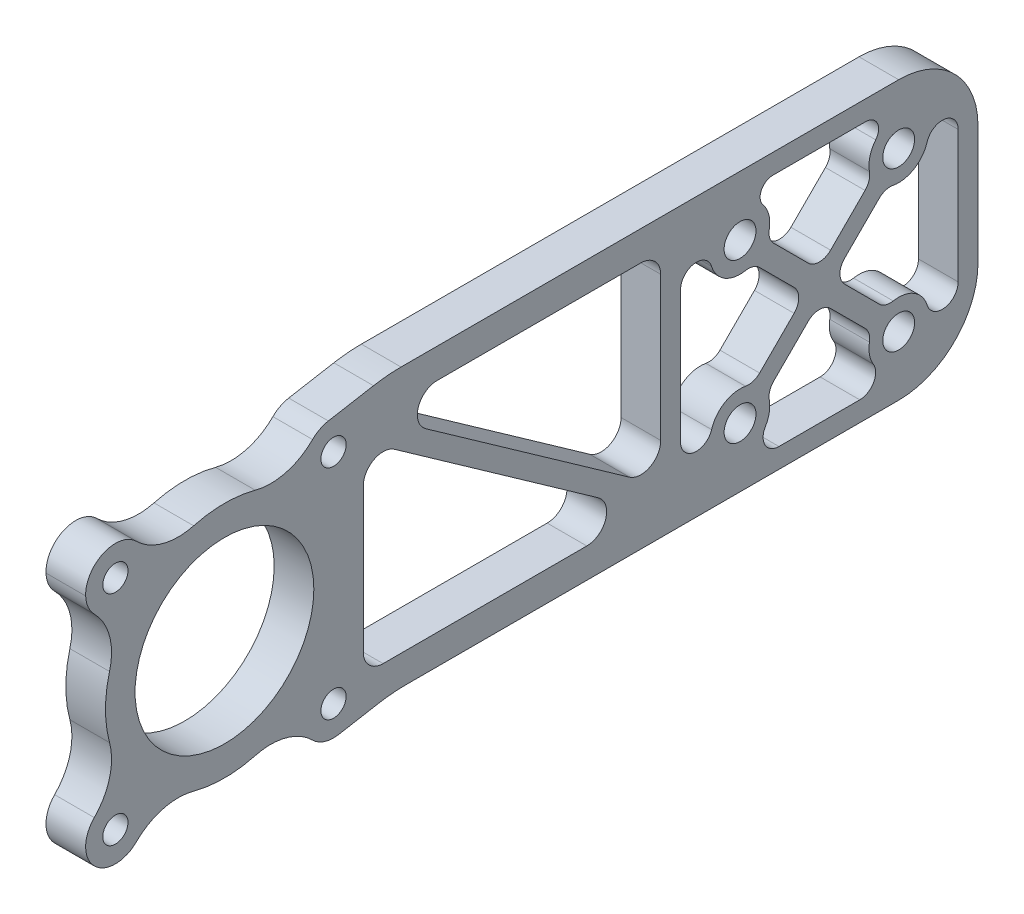
SolidWorks part; units mm, degrees
material "6061-T6 (SS)"
ref_plane "Front" through (0, 0, 0) normal (0, 0, 1) x (1, 0, 0)
ref_plane "Top" through (0, 0, 0) normal (0, 1, 0) x (1, 0, 0)
ref_plane "Right" through (0, 0, 0) normal (1, 0, 0) x (0, 0, -1)
sketch "Sketch1" plane through (0, 0, 0) normal (1, 0, 0) x (0, 0, -1)
  line L0 (0, -23.8125) -> (0, 23.8125)
  line L3 (0, 23.8125) -> (-144.4879, 23.8125)
  line L4 (-144.4879, -23.8125) -> (0, -23.8125)
  line L5 (-144.4879, 23.8125) -> (-144.4879, -23.8125)
  line L6 (-120.65, 23.8125) -> (-120.65, -23.8125) construction
  circle A1 centre (-120.65, 0) radius 14.3129
  point P4 (0, 0)
  dimension "D3" = 28.6258
  dimension "D1" = 9.525
  dimension "D2" = 47.625
  dimension "D5" = 120.65
extrude "Boss-Extrude1" add sketch "Sketch1" along normal blind 6.35
fillet "Fillet1" radius 12.7 4 edges at (3.175, -23.8125, 144.4879) (3.175, 23.8125, 144.4879) (3.175, -23.8125, 0) (3.175, 23.8125, 0)
sketch "Sketch4" plane through (0, 0, 0) normal (-1, 0, 0) x (0, 0, 1)
  point P0 (103.1875, 17.4625)
  point P3 (138.1125, 17.4625)
  point P6 (138.1125, -17.4625)
  point P9 (103.1875, -17.4625)
hole_wizard "#10-32 Tapped Hole1" positions "Sketch4" profile "Sketch3" tap size "#10-32" standard "ANSI Inch" end condition up to next
sketch "Sketch3" plane through (0, 17.4625, 103.1875) normal (0, 1, 0) x (0, 0, 1)
  line L0 (0, 0) -> (0, 6.35)
  line L1 (0, 6.35) -> (2.0193, 6.35)
  line L2 (2.0193, 6.35) -> (2.0193, 0)
  line L5 (2.0193, 0) -> (0, 0)
  line L11 (0, -6.35) -> (0, 107.95) construction
  dimension "Thru Tap Drill Dia." = 4.0386
  dimension "Thru Tap Drill Depth" = 6.35
cosmetic thread "Hole Thread5" parameters "D2"=4.826
cosmetic thread "Hole Thread6" parameters "D2"=4.826
cosmetic thread "Hole Thread7" parameters "D2"=4.826
cosmetic thread "Hole Thread8" parameters "D2"=4.826
sketch "Sketch7" plane through (6.35, 0, 0) normal (1, 0, 0) x (0, 0, -1)
  line L0 (-50.8, 23.8125) -> (-50.8, -23.8125) construction
  line L1 (-12.7, 23.8125) -> (-131.7879, 23.8125) construction
  line L2 (-131.7879, -23.8125) -> (-12.7, -23.8125) construction
  line L4 (0, -11.1125) -> (0, 11.1125) construction
  line L5 (-50.8, -23.8125) -> (-38.1, -11.1125) construction
  line L8 (-12.7, -11.1125) -> (0, -23.8125) construction
  line L9 (0, -11.1125) -> (0, 11.1125) construction
  line L10 (-131.7879, -23.8125) -> (-12.7, -23.8125) construction
  point P0 (-12.7, 14.2875)
  point P2 (-38.1, 14.2875)
  point P4 (-38.1, -11.1125)
  point P6 (-12.7, -11.1125)
  dimension "D1" = 50.8
  dimension "D2" = 25.4
  dimension "D3" = 25.4
  dimension "D4" = 12.7
hole_wizard "#10 Clearance Hole1" positions "Sketch7" profile "Sketch6" hole size "#10" standard "ANSI Inch" end condition up to next
sketch "Sketch6" plane through (6.35, 14.2875, 12.7) normal (0, 1, 0) x (0, 0, -1)
  line L0 (0, 0) -> (0, 6.35)
  line L1 (0, 6.35) -> (2.5527, 6.35)
  line L2 (2.5527, 6.35) -> (2.5527, 0)
  line L5 (2.5527, 0) -> (0, 0)
  line L11 (0, -6.35) -> (0, 107.95) construction
  dimension "Thru Hole Dia." = 5.1054
  dimension "Thru Hole Depth" = 6.35
sketch "Sketch9" plane through (6.35, 0, 0) normal (1, 0, 0) x (0, 0, -1)
  line L0 (0, -20.6375) -> (-89.738, -20.6375)
  line L1 (0, -11.1125) -> (0, 11.1125) construction
  line L2 (-131.7879, -23.8125) -> (-12.7, -23.8125) construction
  arc A0 (-89.738, -20.6375) -> (-96.8375, -23.8125) centre (-89.738, -30.1625) ccw
  circle A1 centre (-103.1875, -17.4625) radius 2.0193 construction
  dimension "D1" = 9.525
  dimension "D3" = 6.35
  dimension "D2" = 3.175
extrude "Cut-Extrude2" cut sketch "Sketch9" against normal through all and the other way through all
other "DeleteFace1" face at (3.175, -16.1064, 1.6373) and patch yes
fillet "Fillet3" radius 12.7 2 edges at (3.175, -20.6375, 0) (3.175, -23.8125, 96.8375)
sketch "Sketch8" plane through (6.35, 0, 0) normal (1, 0, 0) x (0, 0, -1)
  line L0 (-86.5918, 19.05) -> (-53.975, 19.05)
  line L1 (-98.425, 10.3281) -> (-98.425, -12.7)
  line L3 (-95.25, -15.875) -> (-62.6332, -15.875)
  line L4 (-50.8, -7.1531) -> (-50.8, 15.875)
  line L6 (-12.7, 23.8125) -> (-131.7879, 23.8125) construction
  line L8 (0, -7.9375) -> (0, 11.1125) construction
  line L9 (-88.423, 13.2813) -> (-55.8062, -9.7468)
  line L10 (-60.802, -10.1063) -> (-93.4188, 12.9218)
  line L11 (-98.425, 16.4563) -> (-96.5938, 19.05) construction
  line L16 (-33.8025, 12.235) -> (-25.4, 3.8326)
  line L17 (-16.9975, -9.06) -> (-25.4, -0.6576)
  line L18 (-16.9975, 12.235) -> (-25.4, 3.8326)
  line L19 (-14.7525, 9.99) -> (-23.1549, 1.5875)
  line L20 (-23.1549, 1.5875) -> (-14.7525, -6.815)
  line L21 (-27.6451, 1.5875) -> (-36.0475, 9.99)
  line L22 (-27.6451, 1.5875) -> (-36.0475, -6.815)
  line L23 (-25.4, -0.6576) -> (-33.8025, -9.06)
  line L24 (-32.854, 20.6375) -> (-17.946, 20.6375)
  line L25 (-47.625, 12.1576) -> (-47.625, -8.9826)
  line L26 (-31.8702, -17.4625) -> (-18.9298, -17.4625)
  line L30 (-89.738, -20.6375) -> (-12.7, -20.6375) construction
  line L31 (-3.175, 12.1576) -> (-3.175, -8.9826)
  line L32 (0, -7.9375) -> (0, 11.1125) construction
  circle A0 centre (-103.1875, 17.4625) radius 2.0193 construction
  arc A1 (-93.4188, 12.9218) -> (-98.425, 10.3281) centre (-95.25, 10.3281) ccw
  arc A2 (-98.425, -12.7) -> (-95.25, -15.875) centre (-95.25, -12.7) ccw
  arc A3 (-60.802, -10.1063) -> (-62.6332, -15.875) centre (-62.6332, -12.7) cw
  arc A4 (-55.8062, -9.7468) -> (-50.8, -7.1531) centre (-53.975, -7.1531) ccw
  arc A5 (-53.975, 19.05) -> (-50.8, 15.875) centre (-53.975, 15.875) cw
  arc A6 (-88.423, 13.2813) -> (-86.5918, 19.05) centre (-86.5918, 15.875) cw
  arc A7 (-33.8025, 12.235) -> (-34.4229, 17.3141) centre (-38.1, 14.2875) ccw
  arc A8 (-14.7525, 9.99) -> (-8.1446, 12.8985) centre (-12.7, 14.2875) ccw
  arc A9 (-16.9975, -9.06) -> (-16.7629, -13.5973) centre (-12.7, -11.1125) ccw
  arc A10 (-36.0475, -6.815) -> (-42.6554, -9.7235) centre (-38.1, -11.1125) ccw
  arc A11 (-8.1446, -9.7235) -> (-14.7525, -6.815) centre (-12.7, -11.1125) ccw
  arc A12 (-42.6554, 12.8985) -> (-36.0475, 9.99) centre (-38.1, 14.2875) ccw
  arc A13 (-16.3771, 17.3141) -> (-16.9975, 12.235) centre (-12.7, 14.2875) ccw
  arc A14 (-34.0371, -13.5973) -> (-33.8025, -9.06) centre (-38.1, -11.1125) ccw
  arc A15 (-17.946, 20.6375) -> (-16.3771, 17.3141) centre (-17.946, 18.6055) cw
  arc A16 (-32.854, 20.6375) -> (-34.4229, 17.3141) centre (-32.854, 18.6055) ccw
  arc A17 (-47.625, -8.9826) -> (-42.6554, -9.7235) centre (-45.085, -8.9826) ccw
  arc A18 (-47.625, 12.1576) -> (-42.6554, 12.8985) centre (-45.085, 12.1576) cw
  arc A19 (-34.0371, -13.5973) -> (-31.8702, -17.4625) centre (-31.8702, -14.9225) ccw
  arc A20 (-16.7629, -13.5973) -> (-18.9298, -17.4625) centre (-18.9298, -14.9225) cw
  arc A21 (-3.175, -8.9826) -> (-8.1446, -9.7235) centre (-5.715, -8.9826) cw
  arc A22 (-3.175, 12.1576) -> (-8.1446, 12.8985) centre (-5.715, 12.1576) ccw
  dimension "D6" = 3.175
  dimension "D7" = 9.525
  dimension "D11" = 2.032
  dimension "D13" = 2.54
  dimension "D1" = 4.7625
  dimension "D2" = 4.7625
  dimension "D3" = 50.8
  dimension "D4" = 4.7625
  dimension "D5" = 3.175
  dimension "D8" = 3.175
  dimension "D9" = 3.175
  dimension "D10" = 3.175
  dimension "D12" = 3.175
  dimension "D14" = 3.175
  dimension "D15" = 3.175
extrude "Cut-Extrude1" cut sketch "Sketch8" against normal through all contours A14 A19 L26 A20 A9 L17 L23 | A11 A8 L19 L20 | L24 A16 A7 L16 L18 A13 A15 | A18 L25 A17 A10 L22 L21 A12 | A6 L9 A4 L4 A5 L0 | A3 L10 A1 L1 A2 L3 region at (6.35, 8.2231, 65.5906) region at (6.35, -5.0481, 83.6344) region at (6.35, 14.2145, 25.4) region at (6.35, -10.9458, 25.4) region at (6.35, 1.5875, 10.448) region at (6.35, 1.5875, 40.352)
sketch "Sketch10" plane through (6.35, 0, 0) normal (1, 0, 0) x (0, 0, -1)
  line L0 (-104.0145, 22.1526) -> (-94.601, 23.8125)
  line L1 (-12.7, 23.8125) -> (-131.7879, 23.8125) construction
  line L2 (-102.3605, -22.1526) -> (-93.7677, -20.6375)
  line L3 (-89.738, -20.6375) -> (-12.7, -20.6375) construction
  line L4 (-93.7677, -20.6375) -> (-89.738, -20.6375)
  arc A0 (-134.757, 20.8421) -> (-141.4921, 14.107) centre (-138.1125, 17.4625) ccw
  arc A1 (-104.0145, 22.1526) -> (-106.543, 20.8421) centre (-103.1875, 17.4625) ccw
  arc A2 (-106.543, -20.8421) -> (-102.3605, -22.1526) centre (-103.1875, -17.4625) ccw
  arc A3 (-141.4921, -14.107) -> (-134.757, -20.8421) centre (-138.1125, -17.4625) ccw
  arc A4 (-139.0509, 4.9306) -> (-139.0509, -4.9306) centre (-120.65, 0) ccw
  arc A5 (-134.757, 20.8421) -> (-125.5806, 18.4009) centre (-128.0459, 27.6013) ccw
  arc A6 (-115.7194, 18.4009) -> (-106.543, 20.8421) centre (-113.2541, 27.6013) ccw
  arc A7 (-141.4921, 14.107) -> (-139.0509, 4.9306) centre (-148.2513, 7.3959) cw
  arc A8 (-141.4921, -14.107) -> (-139.0509, -4.9306) centre (-148.2513, -7.3959) ccw
  arc A9 (-134.757, -20.8421) -> (-125.5806, -18.4009) centre (-128.0459, -27.6013) cw
  arc A11 (-115.7194, -18.4009) -> (-106.543, -20.8421) centre (-113.2541, -27.6013) cw
  arc A13 (-115.7194, 18.4009) -> (-125.5806, 18.4009) centre (-120.65, 0) ccw
  arc A15 (-125.5806, -18.4009) -> (-115.7194, -18.4009) centre (-120.65, 0) ccw
  dimension "D1" = 9.525
  dimension "D2" = 38.1
  dimension "D3" = 9.525
  dimension "D4" = 10
  dimension "D5" = 10
extrude "Cut-Extrude3" cut sketch "Sketch10" against normal through all and the other way through all flip side to cut
fillet "Fillet2" radius 2.54 12 edges at (3.175, 1.5875, 27.6451) (3.175, -6.815, 36.0475) (3.175, 12.235, 33.8025) (3.175, 12.235, 16.9975) (3.175, 3.8326, 25.4) (3.175, -0.6576, 25.4) (3.175, -9.06, 16.9975) (3.175, -9.06, 33.8025) (3.175, -6.815, 14.7525) (3.175, 1.5875, 23.1549) (3.175, 9.99, 14.7525) (3.175, 9.99, 36.0475)
other "DeleteFace2" face at (3.175, -19.9386, 140.5787) face at (3.175, 19.9386, 140.5787) and patch yes
fillet "Fillet4" radius 25.4 2 edges at (3.175, 23.8125, 94.601) (3.175, -20.6375, 93.7677)
